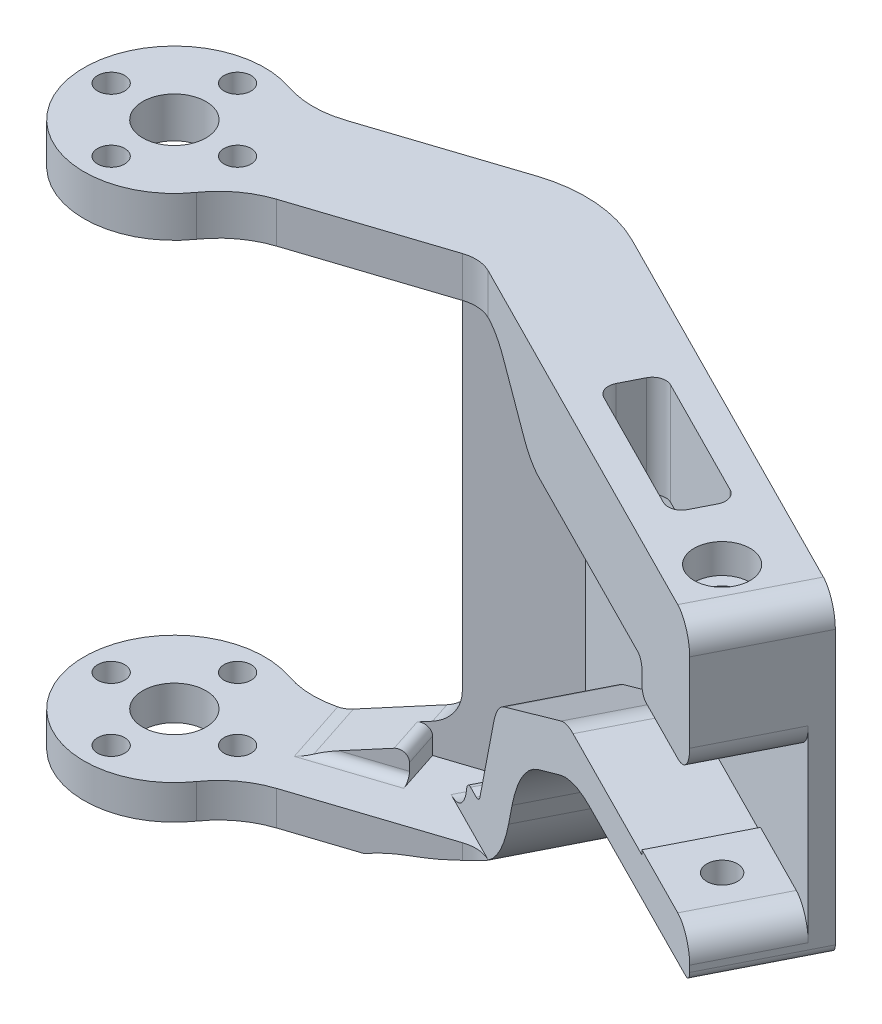
SolidWorks part; units mm, degrees
ref_plane "Front Plane" through (0, 0, 0) normal (0, 0, 1) x (1, 0, 0)
ref_plane "Top Plane" through (0, 0, 0) normal (0, 1, 0) x (1, 0, 0)
ref_plane "Right Plane" through (0, 0, 0) normal (1, 0, 0) x (0, 0, -1)
sketch "草图2" plane through (0, 0, 0) normal (0, 1, 0) x (1, 0, 0)
  line L0 (-35.5061, 0) -> (69.6443, 0) construction
  line L1 (0, 51.4709) -> (0, -34.8439) construction
  line L2 (-33.2307, 28.4265) -> (0, 39.3196)
  line L3 (0, 39.3196) -> (51.1003, 13.4501)
  line L4 (51.1003, 13.4501) -> (51.1003, 0)
  line L5 (51.1003, 0) -> (-0.9854, 26.3683)
  line L6 (-0.9854, 26.3683) -> (-29.4928, 17.0236)
  line L7 (-29.4928, 17.0236) -> (-33.2307, 28.4265)
  line L8 (-31.3618, 22.7251) -> (51.1003, 6.7251) construction
  circle A0 centre (-31.3618, 22.7251) radius 10 construction
  point P19 (-31.3618, 22.7251)
  point P20 (51.1003, 6.7251)
  dimension "D7" = 20
  dimension "D1" = 84
  dimension "D2" = 12
  dimension "D3" = 12
  dimension "D4" = 135
  dimension "D5" = 30
  dimension "D6" = 16
extrude "凸台-拉伸1" add sketch "草图2" along normal blind 3
sketch "草图4" plane through (0, 3, 0) normal (0, 1, 0) x (1, 0, 0)
  line L0 (-33.2307, 28.4265) -> (0, 39.3196)
  line L1 (0, 39.3196) -> (51.1003, 13.4501)
  line L2 (51.1003, 13.4501) -> (51.1003, 10.9501)
  line L3 (51.1003, 0) -> (51.1003, 13.4501) construction
  line L4 (51.1003, 10.9501) -> (0.1569, 36.7402)
  line L5 (0.1569, 36.7402) -> (-32.452, 26.0509)
  line L6 (-33.2307, 28.4265) -> (-29.4928, 17.0236) construction
  line L7 (-32.452, 26.0509) -> (-33.2307, 28.4265)
  dimension "D1" = 2.5
  dimension "D2" = 2.5
extrude "凸台-拉伸2" add sketch "草图4" along normal blind 52
ref_plane "对称面" through (0, 29, 0) normal (0, 1, 0) x (1, 0, 0)
mirror "镜向1" about plane through (0, 29, 0) normal (0, 1, 0) of "凸台-拉伸1"
sketch "草图6" plane through (0, 58, 0) normal (0, 1, 0) x (1, 0, 0)
  line L0 (-33.2307, 28.4265) -> (-29.4928, 17.0236) construction
  circle A0 centre (-31.3618, 22.7251) radius 10
  dimension "D1" = 20
extrude "凸台-拉伸3" add sketch "草图6" against normal blind 3
sketch "草图7" plane through (0, 0, 0) normal (0, -1, 0) x (1, 0, 0)
  circle A0 centre (-31.3618, -22.7251) radius 10
extrude "凸台-拉伸4" add sketch "草图7" against normal up to surface (3 mm away) up to face at (6.5712, 3, -19.5222)
sketch "草图8" plane through (-11.6384, 0, -35.5045) normal (-0.3115, 0, -0.9502) x (-0.9502, 0, 0.3115)
  line L0 (22.7228, 55) -> (22.7228, 3)
  line L1 (22.7228, 3) -> (14.7228, 3)
  line L2 (14.7228, 3) -> (14.7228, 55)
  line L3 (14.7228, 55) -> (22.7228, 55)
extrude "切除-拉伸1" cut sketch "草图8" against normal blind 3
sketch "草图9" plane through (0, 58, 0) normal (0, 1, 0) x (1, 0, 0)
  line L0 (-31.3618, 35.6771) -> (-31.3618, -7.9788) construction
  line L1 (51.1003, 10.648) -> (39.7524, 16.3929) construction
  line L2 (51.1003, 0) -> (51.1003, 13.4501) construction
  line L3 (51.1003, 13.4501) -> (0, 39.3196) construction
  line L4 (41.6064, 10.4105) -> (41.9201, 10.2517) construction
  line L6 (-31.3618, 22.7251) -> (41.6064, 10.4105) construction
  circle A0 centre (41.6064, 10.4105) radius 2
  dimension "D2" = 4
  dimension "D3" = 4.5
  dimension "D1" = 2.5
  dimension "D4" = 74
extrude "切除-拉伸2" cut sketch "草图9" against normal blind 100
sketch "草图10" plane through (0, 58, 0) normal (0, 1, 0) x (1, 0, 0)
  line L0 (-41.3618, 22.7251) -> (-4.1093, 22.7251) construction
  line L1 (-31.3618, 32.7251) -> (-31.3618, 7.7858) construction
  arc A0 (-25.6287, 30.9185) -> (-21.8908, 19.5155) centre (-31.3618, 22.7251) ccw construction
  circle A1 centre (-31.3618, 22.7251) radius 3.5
  circle A2 centre (-31.3618, 29.7251) radius 1.5
  circle A3 centre (-38.3618, 22.7251) radius 1.5
  circle A4 centre (-31.3618, 15.7251) radius 1.5
  circle A5 centre (-24.3618, 22.7251) radius 1.5
  dimension "D1" = 7
  dimension "D2" = 3
  dimension "D3" = 14
  dimension "D4" = 3
  dimension "D5" = 14
extrude "切除-拉伸3" cut sketch "草图10" against normal blind 100
sketch "草图11" plane through (0, 58, 0) normal (0, 1, 0) x (1, 0, 0)
  line L0 (-31.3618, 22.7251) -> (41.6064, 10.4105) construction
sketch "草图12" plane through (-11.6384, 0, -35.5045) normal (-0.3115, 0, -0.9502) x (-0.9502, 0, 0.3115)
  line L0 (18.2224, 29) -> (-18.2224, 29) construction
  line L1 (14.7228, 29) -> (-93.715, 29) construction
  line L2 (14.7228, 55) -> (14.7228, 3) construction
  line L3 (14.7228, 55) -> (32.7228, 55) construction
  line L4 (14.7228, 55) -> (2.7228, 55)
  line L5 (14.7228, 55) -> (14.7228, 3)
  line L6 (14.7228, 3) -> (2.7228, 3)
  line L7 (2.7228, 55) -> (2.7228, 3)
  line L8 (14.7228, 55) -> (2.7228, 3) construction
  line L9 (14.7228, 3) -> (2.7228, 55) construction
  point P10 (8.7228, 29)
  dimension "D2" = 12
extrude "切除-拉伸4" cut sketch "草图12" against normal blind 10
sketch "草图13" plane through (0, 58, 0) normal (0, 1, 0) x (1, 0, 0)
  line L0 (51.1003, 13.4501) -> (45.6803, 2.7439)
  line L1 (51.1003, 0) -> (51.1003, 13.4501) construction
  line L2 (51.1003, 13.4501) -> (0, 39.3196) construction
  line L3 (-0.9854, 26.3683) -> (51.1003, 0) construction
  line L4 (45.6803, 2.7439) -> (51.1003, 0)
  line L5 (51.1003, 0) -> (51.1003, 13.4501)
extrude "切除-拉伸5" cut sketch "草图13" against normal blind 100
sketch "草图14" plane through (0, 55, 0) normal (0, -1, 0) x (1, 0, 0)
  line L0 (45.6803, -2.7439) -> (36.7585, -7.2606)
  line L1 (-0.9854, -26.3683) -> (45.6803, -2.7439) construction
  line L2 (36.7585, -7.2606) -> (41.1711, -15.9768)
  line L3 (41.1711, -15.9768) -> (50.0929, -11.4601)
  line L4 (50.0929, -11.4601) -> (45.6803, -2.7439)
  line L5 (50.0929, -11.4601) -> (45.6803, -2.7439) construction
  line L7 (45.6803, -2.7439) -> (36.7585, -7.2606)
  line L8 (0.1569, -36.7402) -> (50.0929, -11.4601) construction
  circle A0 centre (41.6064, -10.4105) radius 2
  line M6 (0.1569, -36.7402) -> (50.0929, -11.4601)
  line M8 (45.6803, -2.7439) -> (-0.9854, -26.3683)
  circle M19 centre (41.6064, -10.4105) radius 2
  dimension "D1" = 10
extrude "凸台-拉伸5" add sketch "草图14" along normal blind 2.7 contours L3 L4 L2 M19 M8 M6 region at (43.6942, 55, -9.2053)
sketch "草图15" plane through (0, 3, 0) normal (0, 1, 0) x (1, 0, 0)
  line L0 (45.6803, 2.7439) -> (50.0929, 11.4601)
  line L1 (51.1003, 13.4501) -> (45.6803, 2.7439) construction
  line L2 (50.0929, 11.4601) -> (41.1711, 15.9768)
  line L3 (41.1711, 15.9768) -> (36.7585, 7.2606)
  line L4 (-0.9854, 26.3683) -> (45.6803, 2.7439) construction
  line L5 (36.7585, 7.2606) -> (45.6803, 2.7439)
  line L6 (0.1569, 36.7402) -> (50.0929, 11.4601) construction
  circle A0 centre (41.6064, 10.4105) radius 2
  dimension "D1" = 10
extrude "凸台-拉伸6" add sketch "草图15" along normal blind 2
sketch "草图16" plane through (15.8447, 0, -31.2982) normal (0.4517, 0, -0.8922) x (-0.8922, 0, -0.4517)
  line L0 (17.7594, 29) -> (-62.5923, 29) construction
  line L1 (17.7594, 58) -> (17.7594, 0) construction
  line L2 (-0.2406, 58) -> (-0.2406, -1.5067) construction
  line L3 (38.2447, 58) -> (-32.4185, 58) construction
  line L4 (17.7594, 58) -> (8.0764, 41.2285)
  line L5 (8.0764, 41.2285) -> (-0.2406, 39)
  line L6 (-0.2406, 39) -> (-39.516, 39)
  line L7 (-39.516, 58) -> (-39.516, 0) construction
  line L8 (17.7594, 0) -> (8.0764, 16.7715)
  line L9 (8.0764, 16.7715) -> (-0.2406, 19)
  line L10 (-0.2406, 19) -> (-39.516, 19)
  line L11 (-39.516, 19) -> (-39.516, 39)
  line L12 (17.7594, 58) -> (17.7594, 0)
  line L13 (17.7594, 58) -> (-39.516, 58)
  line L14 (-39.516, 58) -> (-39.516, 39)
  line L15 (17.7594, 0) -> (-39.516, 0)
  line L16 (-39.516, 0) -> (-39.516, 19)
  dimension "D1" = 18
  dimension "D2" = 20
  dimension "D3" = 135
  dimension "D4" = 30
sketch "草图18" plane through (14.8373, 0, -29.3083) normal (-0.4517, 0, 0.8922) x (0.8922, 0, 0.4517)
  line L0 (-12.7889, 58) -> (-12.7889, 0) construction
  line L8 (-12.7889, 58) -> (39.516, 58)
  line L10 (-12.7889, 0) -> (39.516, 0)
  line L12 (-16.4544, 29) -> (56.2175, 29) construction
  line L13 (-16.4544, 55) -> (-16.4544, 3) construction
  line L14 (-16.4544, 38.24) -> (66.7647, 38.24) construction
  line L15 (39.516, 48.24) -> (-0.484, 48.24)
  line L16 (39.516, 5) -> (39.516, 52.3) construction
  line L17 (-0.484, 48.24) -> (-12.7889, 58)
  line L18 (39.516, 28.24) -> (9.516, 28.24)
  line L19 (-12.7889, 0) -> (-5.7099, 19.4493)
  line L20 (39.516, 48.24) -> (39.516, 28.24)
  line L21 (-12.7889, 58) -> (-12.7889, 0)
  line L22 (-12.7889, 0) -> (-12.7889, 58)
  line L23 (39.516, 58) -> (39.516, 48.24)
  line L24 (39.516, 0) -> (39.516, 28.24)
  line L25 (-5.7099, 19.4493) -> (9.516, 28.24)
  line M8 (29.516, 3) -> (29.516, 5)
  line M9 (29.516, 5) -> (39.516, 5)
  line M10 (39.516, 5) -> (39.516, 52.3)
  line M11 (39.516, 52.3) -> (29.516, 52.3)
  line M12 (29.516, 52.3) -> (29.516, 55)
  line M13 (29.516, 55) -> (-16.4544, 55)
  line M15 (-16.4544, 3) -> (29.516, 3)
  dimension "D1" = 9.24
  dimension "D2" = 20
  dimension "D3" = 40
  dimension "D4" = 30
  dimension "D5" = 140
  dimension "D6" = 20
extrude "切除-拉伸7" cut sketch "草图18" against normal mid plane 500 contours M10 M11 M12 M13 | L8 M13 M12 M11 | M15 M8 M9 M10 | L10 M9 M8 M15 region at (30.3257, 56.0842, -21.4673) region at (28.7652, 51.5379, -22.2573) region at (29.1285, 1.7806, -22.0734) region at (29.6024, 14.9247, -21.8334)
sketch "草图19" plane through (15.8447, 0, -31.2982) normal (0.4517, 0, -0.8922) x (-0.8922, 0, -0.4517)
  line L1 (-39.516, 28.24) -> (-9.516, 28.24)
  line L4 (-9.516, 28.24) -> (5.7099, 19.4493)
  line L8 (28.3452, 29) -> (-80.8757, 29) construction
  line L9 (28.3452, 55) -> (28.3452, 3) construction
  line L16 (12.7889, 58) -> (0.484, 48.24)
  line L17 (0.484, 48.24) -> (-39.516, 48.24)
  line L18 (-39.516, 48.24) -> (-39.516, 51.24)
  line L19 (-39.516, 51.24) -> (-0.5613, 51.24)
  line L20 (12.7889, 58) -> (7.9613, 58)
  line L21 (7.9613, 58) -> (-0.5613, 51.24)
  line L22 (9.0066, 55) -> (0.484, 48.24) construction
  line L29 (5.7099, 19.4493) -> (12.7889, 0)
  line L30 (12.7889, 0) -> (9.5963, 0)
  line L31 (9.5963, 0) -> (3.2643, 17.3972)
  line L32 (3.2643, 17.3972) -> (-10.3199, 25.24)
  line L33 (-10.3199, 25.24) -> (-39.516, 25.24)
  line L34 (-39.516, 25.24) -> (-39.516, 28.24)
  dimension "D1" = 3
  dimension "D2" = 3
  dimension "D3" = 3
  dimension "D4" = 3
  dimension "D5" = 3
extrude "凸台-拉伸7" add sketch "草图19" against normal up to surface (12 mm away) up to face at (0.1395, 56, -25.7989)
sketch "草图25" plane through (0, 51.24, 0) normal (0, 1, 0) x (1, 0, 0)
  line L0 (49.9712, 11.2196) -> (34.056, 19.2767) construction
  line L1 (45.6803, 2.7439) -> (51.1003, 13.4501) construction
  line L2 (16.3455, 31.0447) -> (51.1003, 13.4501) construction
  circle A0 centre (41.6064, 10.4105) radius 1.7
  circle A1 centre (-31.3618, 22.7251) radius 3.5 construction
  dimension "D1" = 3.4
  dimension "D2" = 74
  dimension "D4" = 4.5
  dimension "D3" = 2.5
extrude "切除-拉伸10" cut sketch "草图25" against normal mid plane 100
sketch "草图26" plane through (0, 48.24, 0) normal (0, -1, 0) x (1, 0, 0)
  line L0 (45.6803, -2.7439) -> (34.9741, -8.1639)
  line L1 (45.6803, -2.7439) -> (19.6319, -15.9309) construction
  line L2 (34.9741, -8.1639) -> (39.3867, -16.8801)
  line L3 (14.4055, -29.5269) -> (50.0929, -11.4601) construction
  line L4 (39.3867, -16.8801) -> (50.0929, -11.4601)
  line L5 (50.0929, -11.4601) -> (45.6803, -2.7439)
  circle A0 centre (41.6064, -10.4105) radius 1.6
  dimension "D1" = 12
extrude "凸台-拉伸11" add sketch "草图26" along normal blind 3.5
sketch "草图27" plane through (0, 28.24, 0) normal (0, 1, 0) x (1, 0, 0)
  line L0 (45.6803, 2.7439) -> (34.9741, 8.1639)
  line L1 (10.9255, 20.3385) -> (45.6803, 2.7439) construction
  line L2 (34.9741, 8.1639) -> (39.3867, 16.8801)
  line L3 (23.3273, 25.0102) -> (50.0929, 11.4601) construction
  line L4 (39.3867, 16.8801) -> (50.0929, 11.4601)
  line L5 (50.0929, 11.4601) -> (45.6803, 2.7439)
  circle A0 centre (41.6064, 10.4105) radius 1.6
  dimension "D1" = 12
extrude "凸台-拉伸12" add sketch "草图27" along normal blind 1.2
sketch "草图24" plane through (-11.6384, 0, -35.5045) normal (-0.3115, 0, -0.9502) x (-0.9502, 0, 0.3115)
  line L0 (10.7228, 55) -> (2.7228, 49)
  line L1 (14.7228, 55) -> (2.7228, 55) construction
  line L2 (2.7228, 55) -> (2.7228, 3) construction
  line L3 (2.7228, 49) -> (2.7228, 55)
  line L4 (2.7228, 55) -> (10.7228, 55)
  line L5 (2.7228, 29) -> (28.9948, 29) construction
  line L6 (2.7228, 9) -> (2.7228, 3)
  line L7 (10.7228, 3) -> (2.7228, 9)
  line L8 (2.7228, 3) -> (10.7228, 3)
  dimension "D1" = 8
  dimension "D2" = 6
extrude "凸台-拉伸10" add sketch "草图24" against normal up to surface (2.5 mm away) up to face at (-6.645, 29, -34.5105)
sketch "草图28" plane through (10.4247, 0, -20.592) normal (-0.4517, 0, 0.8922) x (0.8922, 0, 0.4517)
  line L0 (-7.9613, 58) -> (0.5613, 51.24)
  line L1 (0.5613, 51.24) -> (39.516, 51.24)
  line L2 (39.516, 51.24) -> (39.516, 58)
  line L3 (39.516, 58) -> (-7.9613, 58)
extrude "凸台-拉伸14" add sketch "草图28" against normal up to surface (12 mm away) up to face at (19.1728, 31.8175, -29.6134)
sketch "草图29" plane through (0, 25.24, 0) normal (0, -1, 0) x (1, 0, 0)
  circle A0 centre (41.6064, -10.4105) radius 1.7
  dimension "D1" = 3.4
extrude "切除-拉伸11" cut sketch "草图29" against normal blind 60
fillet "圆角5" radius 15 1 edges at (0, 29, -39.3196)
fillet "圆角6" radius 15 3 edges at (22.3419, 25.24, -21.284) (10.2224, 17.3972, -27.4195) (4.573, 0, -30.2795)
sketch "草图30" plane through (14.8373, 0, -29.3083) normal (-0.4517, 0, 0.8922) x (0.8922, 0, 0.4517)
  line L0 (-16.4544, 3) -> (-11.697, 3)
  line L1 (-11.697, 3) -> (-5.7099, 19.4493)
  line L2 (-5.7099, 19.4493) -> (9.516, 28.24)
  line L3 (9.516, 28.24) -> (27.516, 28.24)
  line L4 (27.516, 28.24) -> (27.516, 29.44)
  line L5 (27.516, 29.44) -> (8.5945, 29.44)
  line L6 (8.5945, 29.44) -> (-8.9537, 19.3086)
  line L7 (-8.9537, 19.3086) -> (-13.4336, 7)
  line L8 (-13.4336, 7) -> (-16.4544, 7)
  line L9 (-16.4544, 55) -> (-16.4544, 3) construction
  line L10 (-16.4544, 7) -> (-16.4544, 3)
  dimension "D1" = 4
  dimension "D2" = 3
  dimension "D3" = 1.5
extrude "凸台-拉伸15" add sketch "草图30" along normal up to surface (9.7695 mm away) up to face at (17.5618, 18.5107, -16.9789)
fillet "圆角8" radius 4 1 edges at (-2.0494, 3, -32.3821)
fillet "圆角9" radius 1 2 edges at (0.6457, 7, -31.0177) (-2.0494, 7, -32.3821)
fillet "圆角10" radius 6 4 edges at (12.1992, 48.24, -25.1687) (4.5954, 55, -29.0182) (20.2989, 29.44, -21.0683) (4.6427, 19.3086, -28.9942)
fillet "圆角12" radius 4 2 edges at (-0.9854, 2.451, -26.3683) (-0.9854, 56.5, -26.3683)
sketch "草图32" plane through (-11.6384, 0, -35.5045) normal (-0.3115, 0, -0.9502) x (-0.9502, 0, 0.3115)
  line L0 (10.7228, 55) -> (2.7228, 49)
  line L1 (2.7228, 49) -> (2.7228, 9)
  line L2 (2.7228, 9) -> (10.7228, 3)
  line L3 (-0.7772, 50.75) -> (10.7228, 55)
  line L4 (-0.7772, 50.75) -> (-0.7772, 7.25)
  line L5 (-0.7772, 7.25) -> (10.7228, 3)
  line L6 (8.6228, 57.8) -> (-0.7772, 50.75) construction
  line L8 (-0.7772, 7.25) -> (8.6228, 0.2) construction
  dimension "D1" = 3.5
extrude "切除-拉伸13" cut sketch "草图32" against normal blind 10
fillet "圆角13" radius 4 4 edges at (-21.4384, 3, -30.9767) (-10.5105, 7.25, -34.5588) (-10.5105, 50.75, -34.5588) (-21.4384, 55, -30.9767)
sketch "草图34" plane through (-10.8597, 0, -33.1289) normal (0.3115, 0, 0.9502) x (0.9502, 0, -0.3115)
  line L0 (-1.8362, 51.7158) -> (-1.8362, 55)
  line L1 (-1.8362, 6.2842) -> (-1.8362, 3)
  line L6 (11.5934, 55) -> (-11.4383, 55)
  line L7 (-10.0517, 54.752) -> (-1.8362, 51.7158)
  line L8 (0.7772, 47.9638) -> (0.7772, 10.0362)
  line L9 (-1.8362, 6.2842) -> (-10.0517, 3.248)
  line L10 (-11.4383, 3) -> (5.9366, 3)
  line L11 (11.5934, 6.438) -> (11.5934, 55)
  line L12 (-1.8362, 55) -> (-11.4383, 55)
  line L13 (-10.0517, 54.752) -> (-1.8362, 51.7158)
  line L15 (-1.8362, 6.2842) -> (-10.0517, 3.248)
  line L16 (-11.4383, 3) -> (-1.8362, 3)
  arc A4 (-10.0517, 54.752) -> (-11.4383, 55) centre (-11.4383, 51) ccw
  arc A5 (0.7772, 47.9638) -> (-1.8362, 51.7158) centre (-3.2228, 47.9638) ccw
  arc A6 (-1.8362, 6.2842) -> (0.7772, 10.0362) centre (-3.2228, 10.0362) ccw
  arc A7 (-11.4383, 3) -> (-10.0517, 3.248) centre (-11.4383, 7) ccw
  arc A8 (-10.0517, 54.752) -> (-11.4383, 55) centre (-11.4383, 51) ccw
  arc A11 (-11.4383, 3) -> (-10.0517, 3.248) centre (-11.4383, 7) ccw
  ellipse E2 centre (5.9366, 7) end of major axis (11.5934, 7) minor radius 4 (5.9366, 3) -> (11.4791, 6.2) ccw
  ellipse E3 centre (12.8648, 6) end of major axis (11.4506, 6) minor radius 1 (11.5934, 6.438) -> (11.4791, 6.2) ccw
  dimension "D1" = 0
extrude "凸台-拉伸16" add sketch "草图34" along normal blind 4
fillet "圆角14" radius 1 2 edges at (-15.9207, 3, -27.2605) (-11.9815, 6.2842, -30.6565)
fillet "圆角15" radius 1 2 edges at (-15.9207, 55, -27.2605) (-11.9815, 51.7158, -30.6565)
fillet "圆角16" radius 10 4 edges at (-25.6287, 56.5, -30.9185) (-25.6287, 1.5, -30.9185) (-21.8908, 1.5, -19.5155) (-21.8908, 56.5, -19.5155)
sketch "草图36" plane through (0, 58, 0) normal (0, 1, 0) x (1, 0, 0)
  line L5 (51.1003, 13.4501) -> (5.5433, 36.5133)
  line L6 (-5.9041, 37.3843) -> (-21.8277, 32.1645)
  line L7 (-18.0898, 20.7615) -> (-2.5598, 25.8523)
  line L8 (0.4929, 25.62) -> (45.6803, 2.7439)
  line L9 (45.6803, 2.7439) -> (51.1003, 13.4501)
  line L10 (51.1003, 13.4501) -> (5.5433, 36.5133)
  line L11 (-5.9041, 37.3843) -> (-21.8277, 32.1645)
  line L12 (-18.0898, 20.7615) -> (-2.5598, 25.8523)
  line L13 (0.4929, 25.62) -> (45.6803, 2.7439)
  line L14 (45.6803, 2.7439) -> (51.1003, 13.4501)
  circle A0 centre (41.6064, 10.4105) radius 1.7
  circle A1 centre (-31.3618, 22.7251) radius 3.5
  circle A2 centre (-24.3618, 22.7251) radius 1.5
  circle A3 centre (-38.3618, 22.7251) radius 1.5
  circle A4 centre (-31.3618, 15.7251) radius 1.5
  arc A5 (5.5433, 36.5133) -> (-5.9041, 37.3843) centre (-1.2317, 23.1305) ccw
  arc A6 (-28.1522, 32.196) -> (-21.8277, 32.1645) centre (-24.9427, 41.6669) ccw
  arc A7 (-28.1522, 32.196) -> (-23.1683, 16.992) centre (-31.3618, 22.7251) ccw
  arc A8 (-18.0898, 20.7615) -> (-23.1683, 16.992) centre (-14.9749, 11.259) ccw
  arc A9 (0.4929, 25.62) -> (-2.5598, 25.8523) centre (-1.3138, 22.0513) ccw
  arc A10 (5.5433, 36.5133) -> (-5.9041, 37.3843) centre (-1.2317, 23.1305) ccw
  arc A11 (-28.1522, 32.196) -> (-21.8277, 32.1645) centre (-24.9427, 41.6669) ccw
  arc A12 (-28.1522, 32.196) -> (-23.1683, 16.992) centre (-31.3618, 22.7251) ccw
  arc A13 (-18.0898, 20.7615) -> (-23.1683, 16.992) centre (-14.9749, 11.259) ccw
  arc A14 (0.4929, 25.62) -> (-2.5598, 25.8523) centre (-1.3138, 22.0513) ccw
  circle A15 centre (-31.3618, 29.7251) radius 1.5
  dimension "D2" = 3.4
  dimension "D3" = 3
  dimension "D4" = 3
  dimension "D5" = 3
  dimension "D6" = 3
  dimension "D7" = 7
  dimension "D1" = 0
extrude "凸台-拉伸17" add sketch "草图36" along normal blind 1.5
sketch "草图37" plane through (0, 59.5, 0) normal (0, 1, 0) x (1, 0, 0)
  line L0 (48.3903, 8.097) -> (17.2646, 23.8544) construction
  line L1 (45.6803, 2.7439) -> (51.1003, 13.4501) construction
  line L2 (0.4929, 25.62) -> (45.6803, 2.7439) construction
  line L3 (36.2496, 17.3255) -> (20.1903, 25.4556)
  line L4 (20.1903, 25.4556) -> (17.7061, 20.5485)
  line L5 (17.7061, 20.5485) -> (33.7655, 12.4185)
  line L6 (33.7655, 12.4185) -> (36.2496, 17.3255)
  line L7 (51.1003, 13.4501) -> (5.5433, 36.5133) construction
  dimension "D1" = 6
  dimension "D2" = 5.5
  dimension "D3" = 18
  dimension "D4" = 15
extrude "切除-拉伸15" cut sketch "草图37" against normal up to surface (11.26 mm away) up to face at (25.6224, 48.24, -18.3732)
sketch "草图38" plane through (0, 59.5, 0) normal (0, 1, 0) x (1, 0, 0)
  circle A0 centre (41.6064, 10.4105) radius 3.1
  dimension "D1" = 6.2
extrude "切除-拉伸16" cut sketch "草图38" against normal blind 3.26
sketch "草图40" plane through (0, 29.44, 0) normal (0, 1, 0) x (1, 0, 0)
  line L0 (50.0929, 11.4601) -> (39.3867, 16.8801)
  line L1 (39.3867, 16.8801) -> (34.9741, 8.1639)
  line L2 (0.4929, 25.62) -> (45.6803, 2.7439) construction
  line L3 (34.9741, 8.1639) -> (45.6803, 2.7439)
  line L4 (45.6803, 2.7439) -> (50.0929, 11.4601)
  dimension "D1" = 12
extrude "凸台-拉伸19" add sketch "草图40" along normal blind 0.5
sketch "草图41" plane through (0, 29.44, 0) normal (0, -1, 0) x (1, 0, 0)
  circle A0 centre (41.6064, -10.4105) radius 1.7
  dimension "D1" = 3.4
extrude "切除-拉伸17" cut sketch "草图41" against normal blind 6
fillet "圆角17" radius 3 3 edges at (47.8866, 29.94, -7.102) (47.8866, 44.74, -7.102) (48.3903, 59.5, -8.097)
fillet "圆角18" radius 1 3 edges at (48.3903, 25.24, -8.097) (37.1804, 48.24, -12.522) (37.1804, 44.74, -12.522)
fillet "圆角19" radius 1.5 4 edges at (20.1903, 53.87, -25.4556) (17.7061, 53.87, -20.5485) (33.7655, 53.87, -12.4185) (36.2496, 53.87, -17.3255)
sketch "草图42" plane through (0, 0, 0) normal (0, -1, 0) x (1, 0, 0)
  line L3 (-3.2971, -37.9877) -> (-10.8097, -23.1479)
  line L4 (-10.8097, -23.1479) -> (-18.0898, -20.7615)
  line L5 (-21.8277, -32.1645) -> (-5.9041, -37.3843)
  line L6 (-3.2971, -37.9877) -> (-10.8097, -23.1479)
  line L7 (-10.8097, -23.1479) -> (-18.0898, -20.7615)
  line L8 (-21.8277, -32.1645) -> (-5.9041, -37.3843)
  circle A1 centre (-31.3618, -22.7251) radius 3.5
  circle A2 centre (-31.3618, -22.7251) radius 3.5
  circle A3 centre (-24.3618, -22.7251) radius 1.5
  circle A4 centre (-24.3618, -22.7251) radius 1.5
  circle A5 centre (-31.3618, -15.7251) radius 1.5
  circle A6 centre (-31.3618, -15.7251) radius 1.5
  circle A7 centre (-38.3618, -22.7251) radius 1.5
  circle A8 centre (-38.3618, -22.7251) radius 1.5
  circle A9 centre (-31.3618, -29.7251) radius 1.5
  circle A10 centre (-31.3618, -29.7251) radius 1.5
  arc A14 (-5.9041, -37.3843) -> (-3.2971, -37.9877) centre (-1.2317, -23.1305) ccw
  arc A15 (-23.1683, -16.992) -> (-18.0898, -20.7615) centre (-14.9749, -11.259) ccw
  arc A16 (-23.1683, -16.992) -> (-28.1522, -32.196) centre (-31.3618, -22.7251) ccw
  arc A17 (-21.8277, -32.1645) -> (-28.1522, -32.196) centre (-24.9427, -41.6669) ccw
  arc A18 (-5.9041, -37.3843) -> (-3.2971, -37.9877) centre (-1.2317, -23.1305) ccw
  arc A19 (-23.1683, -16.992) -> (-18.0898, -20.7615) centre (-14.9749, -11.259) ccw
  arc A20 (-23.1683, -16.992) -> (-28.1522, -32.196) centre (-31.3618, -22.7251) ccw
  arc A21 (-21.8277, -32.1645) -> (-28.1522, -32.196) centre (-24.9427, -41.6669) ccw
  dimension "D1" = 0
  dimension "D2" = 0
  dimension "D3" = 0
  dimension "D4" = 0
  dimension "D5" = 0
  dimension "D6" = 0
extrude "凸台-拉伸20" add sketch "草图42" along normal blind 0.8
fillet "圆角20" radius 10 1 edges at (-7.0534, 0, -30.5678)
